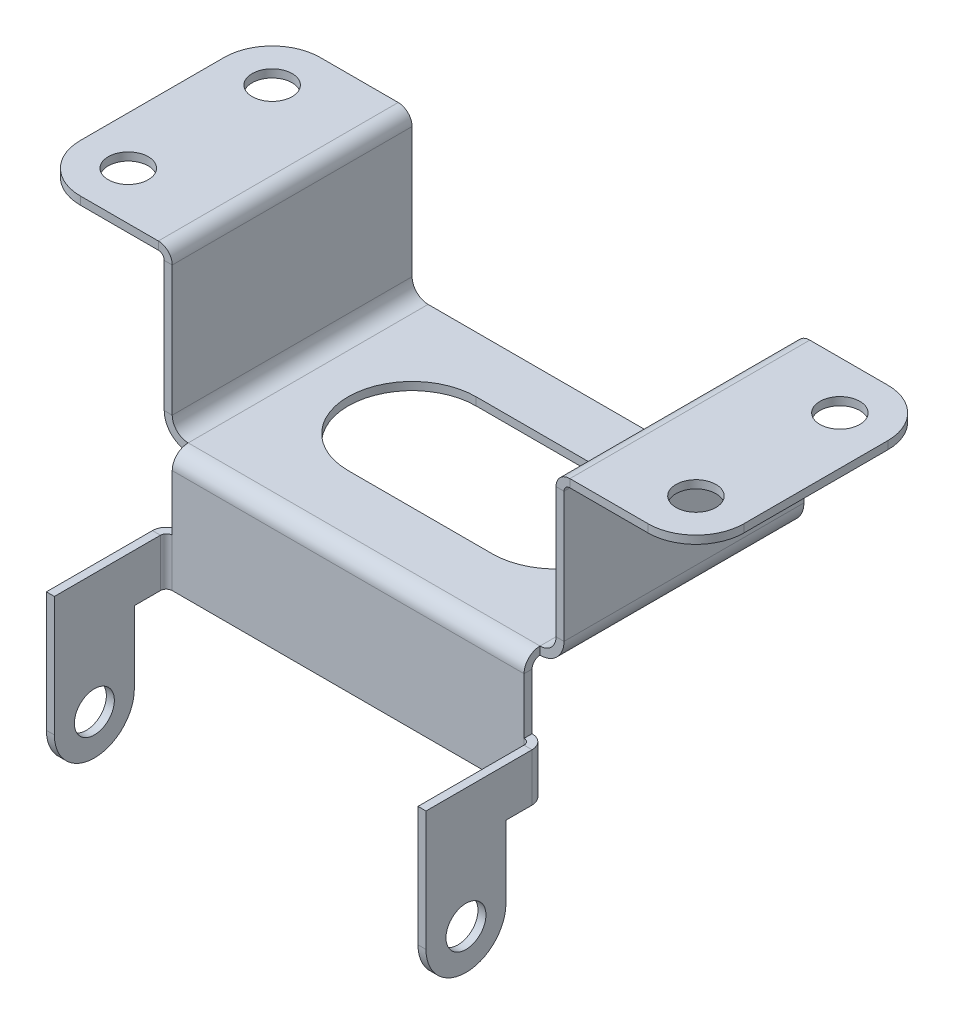
SolidWorks part; units mm, degrees
note: The reader was unsure of these and kept them because the rebuilt part matched: flange length of "Edge-Flange1", "Edge-Flange2", "Edge-Flange3", "Edge-Flange4".
ref_plane "Front Plane" through (0, 0, 0) normal (0, 0, 1) x (1, 0, 0)
ref_plane "Top Plane" through (0, 0, 0) normal (0, 1, 0) x (1, 0, 0)
ref_plane "Right Plane" through (0, 0, 0) normal (1, 0, 0) x (0, 0, -1)
sketch "Sketch1" plane through (0, 0, 0) normal (0, 1, 0) x (1, 0, 0)
  line L1 (-25, -15) -> (25, -15)
  line L2 (-25, -15) -> (-25, 15)
  line L3 (-25, 15) -> (25, 15)
  line L4 (25, -15) -> (25, 15)
  line L5 (-25, -15) -> (25, 15) construction
  line L6 (-25, 15) -> (25, -15) construction
  point P0 (0, 0)
  dimension "D1" = 30
  dimension "D2" = 50
base flange "Base-Flange1" sketch "Sketch1" thickness 1 reverse thickness direction no parameters "D1"=0.7366
edge flange "Edge-Flange1" sketch "Sketch10" flange profiles "Sketch10", "Sketch11" flange angle 90 flange length 20 flange position material inside bend radius 2 thickness 1 relief rectangular parameters "D6"=10, "D8"=1
sketch "Sketch10" plane through (25, 0, 0) normal (1, 0, 0) x (0, 0, -1)
  line L0 (-15, 0) -> (15, 0) construction
  line L1 (-15, 0) -> (15, 0)
  line L2 (-15, 0) -> (-15, 19)
  line L3 (-15, 19) -> (15, 19)
  line L4 (15, 19) -> (15, 0)
sketch "Sketch11" plane through (-25, 0, 0) normal (-1, 0, 0) x (0, 0, 1)
  line L0 (-15, 0) -> (15, 0) construction
  line L1 (-15, 0) -> (15, 0)
  line L2 (-15, 0) -> (-15, 19)
  line L3 (-15, 19) -> (15, 19)
  line L4 (15, 19) -> (15, 0)
bend "EdgeBend1" bend radius 2 bend angle 90 parameters "D5"=1
bend "EdgeBend2" bend radius 2 bend angle 90 parameters "D5"=2
edge flange "Edge-Flange2" sketch "Sketch16" flange profiles "Sketch16", "Sketch17" flange angle 90 flange length 17.5 flange position material outside bend radius 0.7366 thickness 1 relief rectangular parameters "D6"=10, "D8"=1
sketch "Sketch16" plane through (25, 19, 0) normal (0, 1, 0) x (0, 0, 1)
  line L2 (-15, 0) -> (-15, 16.5)
  line L3 (-15, 16.5) -> (15, 16.5)
  line L4 (15, 16.5) -> (15, 0)
  line L7 (-15, 0) -> (15, 0) construction
  line L8 (-15, 0) -> (15, 0)
sketch "Sketch17" plane through (-25, 19, 0) normal (0, 1, 0) x (0, 0, -1)
  line L2 (-15, 0) -> (-15, 16.5)
  line L3 (-15, 16.5) -> (15, 16.5)
  line L4 (15, 16.5) -> (15, 0)
  line L7 (-15, 0) -> (15, 0) construction
  line L8 (-15, 0) -> (15, 0)
bend "EdgeBend3" bend radius 0.7366 bend angle 90 parameters "D5"=3
bend "EdgeBend4" bend radius 0.7366 bend angle 90 parameters "D5"=4
edge flange "Edge-Flange3" sketch "Sketch30" flange angle 90 flange length 15 flange position bend outside bend radius 1 thickness 1 relief rectangular parameters "D6"=10
bend "EdgeBend6" bend radius 1 bend angle 90 parameters "D5"=5
sketch "Sketch30" plane through (0, -1, 15) normal (0, 0, 1) x (-1, 0, 0)
  line L0 (22, 0) -> (-22, 0) construction
  line L1 (22, 0) -> (-22, 0)
  line L2 (-22, 0) -> (-22, 14)
  line L3 (-22, 14) -> (22, 14)
  line L4 (22, 14) -> (22, 0)
edge flange "Edge-Flange4" sketch "Sketch35" flange angle 90 flange length 15 flange position bend outside bend radius 0.7366 thickness 1 relief rectangular parameters "D6"=10, "D8"=1
sketch "Sketch35" plane through (-22, 0, 17) normal (-1, 0, 0) x (0, -1, 0)
  line L0 (9, 0) -> (15, 0)
  line L3 (24, 14) -> (9, 14)
  line L4 (9, 14) -> (9, 0)
  line L7 (2, 0) -> (15, 0) construction
  line L9 (2, -1) -> (15, -1) construction
  line L10 (15, 0) -> (15, -1) construction
  line L11 (24, 4) -> (15, 4)
  line L12 (15, 4) -> (15, 0)
  arc A0 (24, 4) -> (24, 14) centre (24, 9) ccw
  circle A1 centre (24, 9) radius 2.5
  point P2 (23.9152, 9)
  dimension "D4" = 10
  dimension "D5" = 5
  dimension "D1" = 15
  dimension "D2" = 6
  dimension "D3" = 15
bend "EdgeBend7" bend radius 0.7366 bend angle 90 parameters "D5"=6
mirror "Mirror1" about plane through (0, 0, 0) normal (1, 0, 0) of "Edge-Flange4"
bend "MirrorBend1" bend radius 0.7366 bend angle 90 parameters "D5"=7
sketch "Sketch38" plane through (0, 0, 0) normal (0, 1, 0) x (1, 0, 0)
  line L0 (-9, 0) -> (9, 0) construction
  line L1 (-9, 8) -> (9, 8)
  line L2 (-9, -8) -> (9, -8)
  line L3 (0, 0) -> (0, 11.7735) construction
  line L4 (41.5, 15) -> (25.7366, 15) construction
  line L5 (41.5, -15) -> (41.5, 15) construction
  line L6 (41.5, 15) -> (25.7366, 15)
  line L7 (41.5, -15) -> (41.5, 15)
  line L8 (0, 0) -> (20.4574, 0) construction
  arc A0 (-9, 8) -> (-9, -8) centre (-9, 0) ccw
  arc A1 (9, -8) -> (9, 8) centre (9, 0) ccw
  circle A2 centre (35.5, 9) radius 2.5
  circle A3 centre (35.5, 9) radius 6
  circle A4 centre (35.5, -9) radius 2.5
  circle A5 centre (-35.5, 9) radius 2.5
  circle A6 centre (-35.5, -9) radius 2.5
  point P2 (0, 0)
  point P25 (0, 0)
  dimension "D1" = 5
  dimension "D2" = 8
  dimension "D4" = 12
  dimension "D3" = 18
  dimension "D5" = 2
extrude "Cut-Extrude1" cut sketch "Sketch38" against normal through all both and the other way through all contours A5 | A6 | L2 A1 L1 A0 | A2 | A4
fillet "Fillet1" radius 6 4 edges at (-41.5, 19.5, -15) (-41.5, 19.5, 15) (41.5, 19.5, 15) (41.5, 19.5, -15)
sketch "Bend-Lines1" [suppressed] plane through (0, 0, 0) normal (0, 1, 0) x (1, 0, 0)
sketch "Bounding-Box1" [suppressed] plane through (0, 0, 0) normal (0, 1, 0) x (1, 0, 0)
sheet metal parameters "Sheet-Metal1" thickness 1 parameters "D1"=0.7366
flat pattern "Flat-Pattern1" [suppressed]
sketch "Bend-Lines2" plane through (0, 0, 0) normal (0, 1, 0) x (1, 0, 0)
sketch3d "Bounding-Box2" [suppressed]
  line L0 (-25, 15, 0) -> (25, 15, 0) construction
  line L1 (-25, -15, 0) -> (25, -15, 0) construction
  line L2 (-25, 15, 0) -> (-25, -15, 0) construction
  line L3 (25, 15, 0) -> (25, -15, 0) construction
sheet metal parameters "Sheet-Metal2" thickness 1 parameters "D1"=0.7366
flat pattern "Flat-Pattern1"
sketch "Bend-Lines2" plane through (0, 0, 0) normal (0, 1, 0) x (1, 0, 0)
  line L0 (-23.9635, 15) -> (-23.9635, -15) construction
  line L1 (23.9635, -15) -> (23.9635, 15) construction
  line L2 (-23.9635, 15) -> (-23.9635, -15) construction
  line L3 (23.9635, -15) -> (23.9635, 15) construction
sketch3d "Bounding-Box2" [suppressed]
  line L0 (42.927, 15, 0) -> (-42.927, 15, 0) construction
  line L1 (42.927, -15, 0) -> (-42.927, -15, 0) construction
  line L2 (42.927, 15, 0) -> (42.927, -15, 0) construction
  line L3 (-42.927, 15, 0) -> (-42.927, -15, 0) construction
bend of the flat pattern "Flatten-<EdgeBend1>1"
bend of the flat pattern "Flatten-<EdgeBend2>1"
sheet metal parameters "Sheet-Metal3" thickness 1 parameters "D1"=0.7366
flat pattern "Flat-Pattern1"
sketch "Bend-Lines2" plane through (0, 0, 0) normal (0, 1, 0) x (1, 0, 0)
  line L0 (-23.9635, 15) -> (-23.9635, -15) construction
  line L1 (23.9635, -15) -> (23.9635, 15) construction
  line L2 (-23.9635, 15) -> (-23.9635, -15) construction
  line L3 (23.9635, -15) -> (23.9635, 15) construction
  line L4 (-43.1616, 15) -> (-43.1616, -15) construction
  line L5 (43.1616, -15) -> (43.1616, 15) construction
  line L6 (-43.1616, 15) -> (-43.1616, -15) construction
  line L7 (43.1616, -15) -> (43.1616, 15) construction
sketch3d "Bounding-Box2" [suppressed]
  line L0 (59.8962, 15, 0) -> (-59.8962, 15, 0) construction
  line L1 (59.8962, -15, 0) -> (-59.8962, -15, 0) construction
  line L2 (59.8962, 15, 0) -> (59.8962, -15, 0) construction
  line L3 (-59.8962, 15, 0) -> (-59.8962, -15, 0) construction
bend of the flat pattern "Flatten-<EdgeBend1>1"
bend of the flat pattern "Flatten-<EdgeBend2>1"
bend of the flat pattern "Flatten-<EdgeBend3>1"
bend of the flat pattern "Flatten-<EdgeBend4>1"
sheet metal parameters "Sheet-Metal4" thickness 1 parameters "D1"=0.7366
flat pattern "Flat-Pattern1"
sketch "Bend-Lines2" plane through (0, 0, 0) normal (0, 1, 0) x (1, 0, 0)
  line L0 (-23.9635, 15) -> (-23.9635, -15) construction
  line L1 (23.9635, -15) -> (23.9635, 15) construction
  line L2 (-23.9635, 15) -> (-23.9635, -15) construction
  line L3 (23.9635, -15) -> (23.9635, 15) construction
  line L4 (-43.1616, 15) -> (-43.1616, -15) construction
  line L5 (43.1616, -15) -> (43.1616, 15) construction
  line L6 (-43.1616, 15) -> (-43.1616, -15) construction
  line L7 (43.1616, -15) -> (43.1616, 15) construction
  line L10 (-22, -16.1781) -> (22, -16.1781) construction
  line L11 (-22, -16.1781) -> (22, -16.1781) construction
  point P8 (-22, -16.9635)
  point P9 (22, -16.9635)
sketch3d "Bounding-Box2" [suppressed]
  line L0 (59.8962, 15, 0) -> (-59.8962, 15, 0) construction
  line L1 (59.8962, -30.3562, 0) -> (-59.8962, -30.3562, 0) construction
  line L2 (59.8962, 15, 0) -> (59.8962, -30.3562, 0) construction
  line L3 (-59.8962, 15, 0) -> (-59.8962, -30.3562, 0) construction
bend of the flat pattern "Flatten-<EdgeBend1>1"
bend of the flat pattern "Flatten-<EdgeBend2>1"
bend of the flat pattern "Flatten-<EdgeBend3>1"
bend of the flat pattern "Flatten-<EdgeBend4>1"
bend of the flat pattern "Flatten-<EdgeBend6>1"
sheet metal parameters "Sheet-Metal5" thickness 1 parameters "D1"=0.7366
flat pattern "Flat-Pattern1"
sketch "Bend-Lines2" plane through (0, 0, 0) normal (0, 1, 0) x (1, 0, 0)
  line L0 (-23.9635, 15) -> (-23.9635, -15) construction
  line L1 (23.9635, -15) -> (23.9635, 15) construction
  line L2 (-23.9635, 15) -> (-23.9635, -15) construction
  line L3 (23.9635, -15) -> (23.9635, 15) construction
  line L4 (-43.1616, 15) -> (-43.1616, -15) construction
  line L5 (43.1616, -15) -> (43.1616, 15) construction
  line L6 (-43.1616, 15) -> (-43.1616, -15) construction
  line L7 (43.1616, -15) -> (43.1616, 15) construction
  line L9 (-22.9712, -24.3562) -> (-22.9712, -30.3562) construction
  line L10 (-22, -16.1781) -> (22, -16.1781) construction
  line L11 (-22, -16.1781) -> (22, -16.1781) construction
  line L13 (-22.9712, -24.3562) -> (-22.9712, -30.3562) construction
sketch3d "Bounding-Box2" [suppressed]
  line L0 (-59.8962, 15, 0) -> (59.8962, 15, 0) construction
  line L1 (-59.8962, -44.356, 0) -> (59.8962, -44.356, 0) construction
  line L2 (-59.8962, 15, 0) -> (-59.8962, -44.356, 0) construction
  line L3 (59.8962, 15, 0) -> (59.8962, -44.356, 0) construction
bend of the flat pattern "Flatten-<EdgeBend1>1"
bend of the flat pattern "Flatten-<EdgeBend2>1"
bend of the flat pattern "Flatten-<EdgeBend3>1"
bend of the flat pattern "Flatten-<EdgeBend4>1"
bend of the flat pattern "Flatten-<EdgeBend6>1"
bend of the flat pattern "Flatten-<EdgeBend7>1"
sheet metal parameters "Sheet-Metal6" thickness 1 parameters "D1"=0.7366
flat pattern "Flat-Pattern1"
sketch "Bend-Lines2" plane through (0, 0, 0) normal (0, 1, 0) x (1, 0, 0)
  line L0 (-23.9635, 15) -> (-23.9635, -15) construction
  line L1 (23.9635, -15) -> (23.9635, 15) construction
  line L2 (-23.9635, 15) -> (-23.9635, -15) construction
  line L3 (23.9635, -15) -> (23.9635, 15) construction
  line L4 (-43.1616, 15) -> (-43.1616, -15) construction
  line L5 (43.1616, -15) -> (43.1616, 15) construction
  line L6 (-43.1616, 15) -> (-43.1616, -15) construction
  line L7 (43.1616, -15) -> (43.1616, 15) construction
  line L8 (22.9712, -30.3562) -> (22.9712, -24.3562) construction
  line L9 (-22.9712, -24.3562) -> (-22.9712, -30.3562) construction
  line L10 (-22, -16.1781) -> (22, -16.1781) construction
  line L11 (-22, -16.1781) -> (22, -16.1781) construction
  line L12 (22.9712, -30.3562) -> (22.9712, -24.3562) construction
  line L13 (-22.9712, -24.3562) -> (-22.9712, -30.3562) construction
sketch3d "Bounding-Box2" [suppressed]
  line L0 (59.8962, 15, 0) -> (-59.8962, 15, 0) construction
  line L1 (59.8962, -44.356, 0) -> (-59.8962, -44.356, 0) construction
  line L2 (59.8962, 15, 0) -> (59.8962, -44.356, 0) construction
  line L3 (-59.8962, 15, 0) -> (-59.8962, -44.356, 0) construction
bend of the flat pattern "Flatten-<EdgeBend1>1"
bend of the flat pattern "Flatten-<EdgeBend2>1"
bend of the flat pattern "Flatten-<EdgeBend3>1"
bend of the flat pattern "Flatten-<EdgeBend4>1"
bend of the flat pattern "Flatten-<EdgeBend6>1"
bend of the flat pattern "Flatten-<EdgeBend7>1"
bend of the flat pattern "Flatten-<MirrorBend1>1"
sheet metal parameters "Sheet-Metal7" thickness 1 parameters "D1"=0.7366
flat pattern "Flat-Pattern1"
sketch "Bend-Lines2" plane through (0, 0, 0) normal (0, 1, 0) x (1, 0, 0)
  line L0 (-23.9635, 15) -> (-23.9635, -15) construction
  line L1 (23.9635, -15) -> (23.9635, 15) construction
  line L2 (-23.9635, 15) -> (-23.9635, -15) construction
  line L3 (23.9635, -15) -> (23.9635, 15) construction
  line L4 (-43.1616, 15) -> (-43.1616, -15) construction
  line L5 (43.1616, -15) -> (43.1616, 15) construction
  line L6 (-43.1616, 15) -> (-43.1616, -15) construction
  line L7 (43.1616, -15) -> (43.1616, 15) construction
  line L8 (22.9712, -30.3562) -> (22.9712, -24.3562) construction
  line L9 (-22.9712, -24.3562) -> (-22.9712, -30.3562) construction
  line L10 (-22, -16.1781) -> (22, -16.1781) construction
  line L11 (-22, -16.1781) -> (22, -16.1781) construction
  line L12 (22.9712, -30.3562) -> (22.9712, -24.3562) construction
  line L13 (-22.9712, -24.3562) -> (-22.9712, -30.3562) construction
sketch3d "Bounding-Box2" [suppressed]
  line L0 (-59.8962, 15, 0) -> (59.8962, 15, 0) construction
  line L1 (-59.8962, -44.356, 0) -> (59.8963, -44.356, 0) construction
  line L2 (-59.8962, 15, 0) -> (-59.8962, -44.356, 0) construction
  line L3 (59.8962, 15, 0) -> (59.8963, -44.356, 0) construction
bend of the flat pattern "Flatten-<EdgeBend1>1"
bend of the flat pattern "Flatten-<EdgeBend2>1"
bend of the flat pattern "Flatten-<EdgeBend3>1"
bend of the flat pattern "Flatten-<EdgeBend4>1"
bend of the flat pattern "Flatten-<EdgeBend6>1"
bend of the flat pattern "Flatten-<EdgeBend7>1"
bend of the flat pattern "Flatten-<MirrorBend1>1"
